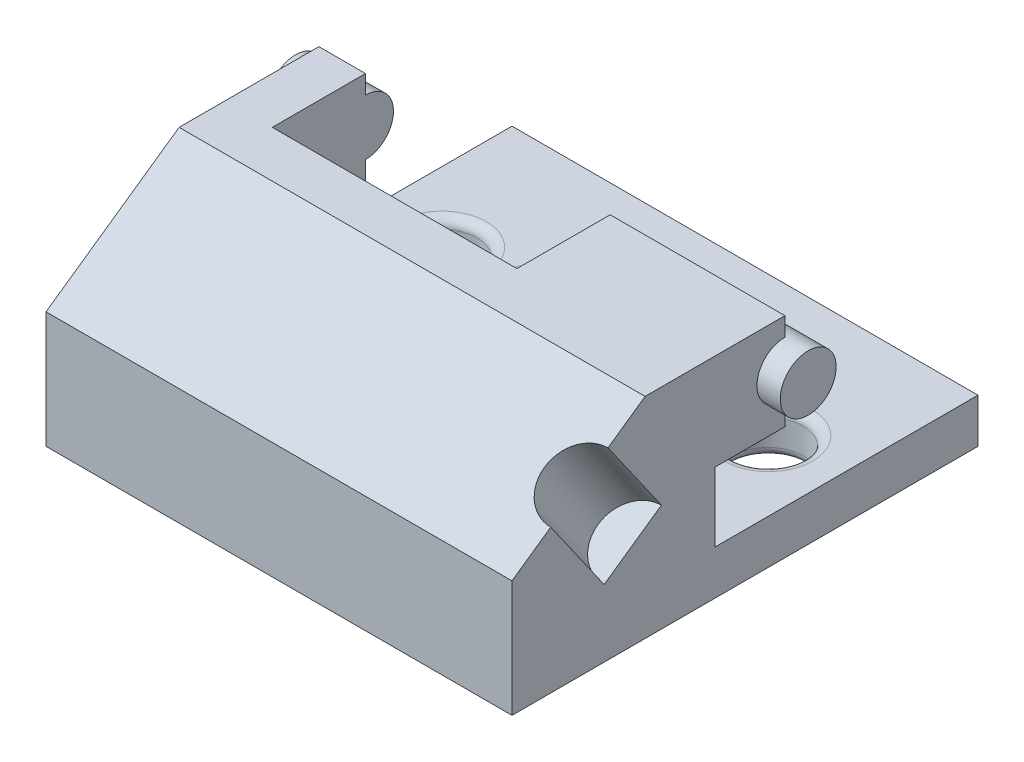
SolidWorks part; units mm, degrees
material "1060 Alloy"
ref_plane "Front Plane" through (0, 0, 0) normal (0, 0, 1) x (1, 0, 0)
ref_plane "Top Plane" through (0, 0, 0) normal (0, 1, 0) x (1, 0, 0)
ref_plane "Right Plane" through (0, 0, 0) normal (1, 0, 0) x (0, 0, -1)
sketch "Sketch1" plane through (0, 0, 0) normal (0, 1, 0) x (1, 0, 0)
  line L0 (-35.4255, 53.6528) -> (-35.4255, -46.3472)
  line L1 (-35.4255, -46.3472) -> (54.5745, -46.3472)
  line L2 (54.5745, -46.3472) -> (64.5745, -36.3472)
  line L3 (64.5745, -36.3472) -> (64.5745, 53.6528)
  line L4 (64.5745, 53.6528) -> (-35.4255, 53.6528)
  line L5 (4.309, 53.6528) -> (4.309, 29.5623)
  line L6 (4.309, 29.5623) -> (0, 29.5623)
  line L7 (0, 29.5623) -> (0, -13.052)
  line L8 (0, -13.052) -> (9.9122, -13.052)
  line L9 (9.9122, -13.052) -> (9.9122, -46.3472)
  line L10 (27.0745, -11.3472) -> (27.0745, 18.6528)
  line L11 (42.0745, 18.6528) -> (42.0745, -11.3472)
  line L12 (42.0745, -11.3472) -> (42.0745, -31.3472) construction
  circle A0 centre (34.5745, 38.6528) radius 7.5
  circle A1 centre (34.5745, -31.3472) radius 7.5
  arc A2 (27.0745, 18.6528) -> (42.0745, 18.6528) centre (34.5745, 18.6528) cw
  arc A3 (42.0745, -11.3472) -> (27.0745, -11.3472) centre (34.5745, -11.3472) cw
  dimension "D1" = 15
  dimension "D9" = 15
  dimension "D2" = 30
  dimension "D3" = 15
  dimension "D4" = 20
  dimension "D5" = 30
  dimension "D6" = 20
  dimension "D7" = 15
  dimension "D8" = 15
  dimension "D10" = 45
  dimension "D11" = 10
  dimension "D12" = 100
sketch "Sketch3" plane through (0, 0, 0) normal (1, 0, 0) x (0, 0, -1)
  line L0 (-58.563, -35) -> (-58.563, -10)
  line L1 (-58.563, -10) -> (-30, 10)
  line L2 (-30, 10) -> (0, 10)
  line L3 (0, 10) -> (0, 6)
  line L4 (0, -10.6436) -> (-15, -10.6436)
  line L5 (-15, -10.6436) -> (-15, -25.495)
  line L6 (-15, -25.495) -> (41.437, -25.495)
  line L7 (41.437, -25.495) -> (41.437, -35)
  line L8 (41.437, -35) -> (-58.563, -35)
  line L9 (-50.2568, -4.184) -> (-38.7853, -20.567)
  line L10 (-38.7853, -20.567) -> (-26.498, -11.9634)
  line L11 (-26.498, -11.9634) -> (-37.9695, 4.4197)
  line L12 (0, -6) -> (0, -10.6436)
  circle A0 centre (0, 0) radius 6
  dimension "D3" = 12
  dimension "D1" = 30
  dimension "D2" = 10
  dimension "D4" = 20
  dimension "D5" = 20
  dimension "D6" = 25
  dimension "D7" = 100
  dimension "D8" = 15
  dimension "D9" = 55
  dimension "D10" = 15
  dimension "D11" = 15
extrude "Boss-Extrude1" add sketch "Sketch3" along normal blind 100 contours A0 L3 L2 L1 L11 L10 L9 L0 L8 L7 L6 L5 L4 L12 | L10 L11 L1 L9 | A0 region at (0, -18.1863, 19.2541) region at (0, -8.0737, 38.3774) region at (0, 0, 0)
extrude "Boss-Extrude2" add sketch "Sketch3<3>" along normal blind 5 from surface contours A0 region at (0, 0, 0) starting at face at (100, -12.0252, 8.0229)
sketch "Sketch3<3>" plane through (0, 0, 0) normal (1, 0, 0) x (0, 0, -1) same geometry as "Sketch3"
extrude "Boss-Extrude3" add sketch "Sketch3<4>" against normal blind 5 contours A0 region at (0, 0, 0)
sketch "Sketch3<4>" plane through (0, 0, 0) normal (1, 0, 0) x (0, 0, -1) same geometry as "Sketch3"
sketch "Sketch4" plane through (0, 10, 0) normal (0, 1, 0) x (1, 0, 0)
  line L0 (62.5, 6) -> (62.5, -20)
  line L1 (105, 6) -> (-5, 6) construction
  line L3 (62.5, -20) -> (10, -20)
  line L4 (10, -20) -> (10, 6)
  line L5 (62.5, 6) -> (10, 6)
  line L7 (100, -30) -> (0, -30) construction
  line L8 (0, -30) -> (0, 0) construction
  dimension "D1" = 10
  dimension "D2" = 52.5
  dimension "D3" = 10
extrude "Cut-Extrude2" cut sketch "Sketch4" against normal up to surface (35.495 mm away) up to face at (50, -25.495, -13.2185)
sketch "Sketch5" plane through (0, 20.8055, 14.5682) normal (0, 0.8192, 0.5736) x (1, 0, 0)
  line L0 (0, -28.5678) -> (100, -28.5678) construction
  line L2 (100, -53.7077) -> (100, -18.8388) construction
  line L4 (0, -43.5678) -> (100, -43.5678) construction
  line L5 (100, -28.5678) -> (100, -43.5678)
  arc A0 (100, -28.5678) -> (100, -43.5678) centre (100, -36.0678) ccw
extrude "Cut-Extrude3" cut sketch "Sketch5" against normal blind 20
sketch "Sketch6" plane through (0, -25.495, 0) normal (0, 1, 0) x (1, 0, 0)
  line L0 (65, 3.937) -> (35, 3.937)
  line L1 (35, 18.937) -> (65, 18.937)
  line L2 (85, 18.937) -> (65, 18.937) construction
  line L3 (85, 3.937) -> (65, 3.937) construction
  line L4 (35, 18.937) -> (35, 3.937) construction
  line L5 (35, 18.937) -> (15, 18.937) construction
  line L6 (35, 3.937) -> (15, 3.937) construction
  line L7 (100, -15) -> (100, 41.437) construction
  circle A0 centre (15, 11.437) radius 7.5
  circle A1 centre (85, 11.437) radius 7.5
  arc A2 (35, 3.937) -> (35, 18.937) centre (35, 11.437) cw
  arc A3 (65, 18.937) -> (65, 3.937) centre (65, 11.437) cw
  dimension "D1" = 15
  dimension "D2" = 30
  dimension "D3" = 20
  dimension "D4" = 15
  dimension "D5" = 30
  dimension "D6" = 20
extrude "Cut-Extrude4" cut sketch "Sketch6" against normal through all
fillet "Fillet1" radius 2 12 edges at (27.5, -35, -11.437) (50, -35, -18.937) (72.5, -35, -11.437) (85, -35, -3.937) (85, -25.495, -3.937) (15, -35, -3.937) (15, -25.495, -3.937) (50, -35, -3.937) (50, -25.495, -18.937) (72.5, -25.495, -11.437) (50, -25.495, -3.937) (27.5, -25.495, -11.437)
sketch "Sketch7" plane through (0, -25.495, 0) normal (0, 1, 0) x (1, 0, 0)
  line L0 (100, 31.437) -> (90, 41.437)
  line L1 (100, -15) -> (100, 41.437) construction
  line L2 (100, 41.437) -> (0, 41.437) construction
  line L3 (100, 31.437) -> (100, 41.437)
  line L4 (100, 41.437) -> (90, 41.437)
  dimension "D1" = 10
  dimension "D2" = 45
